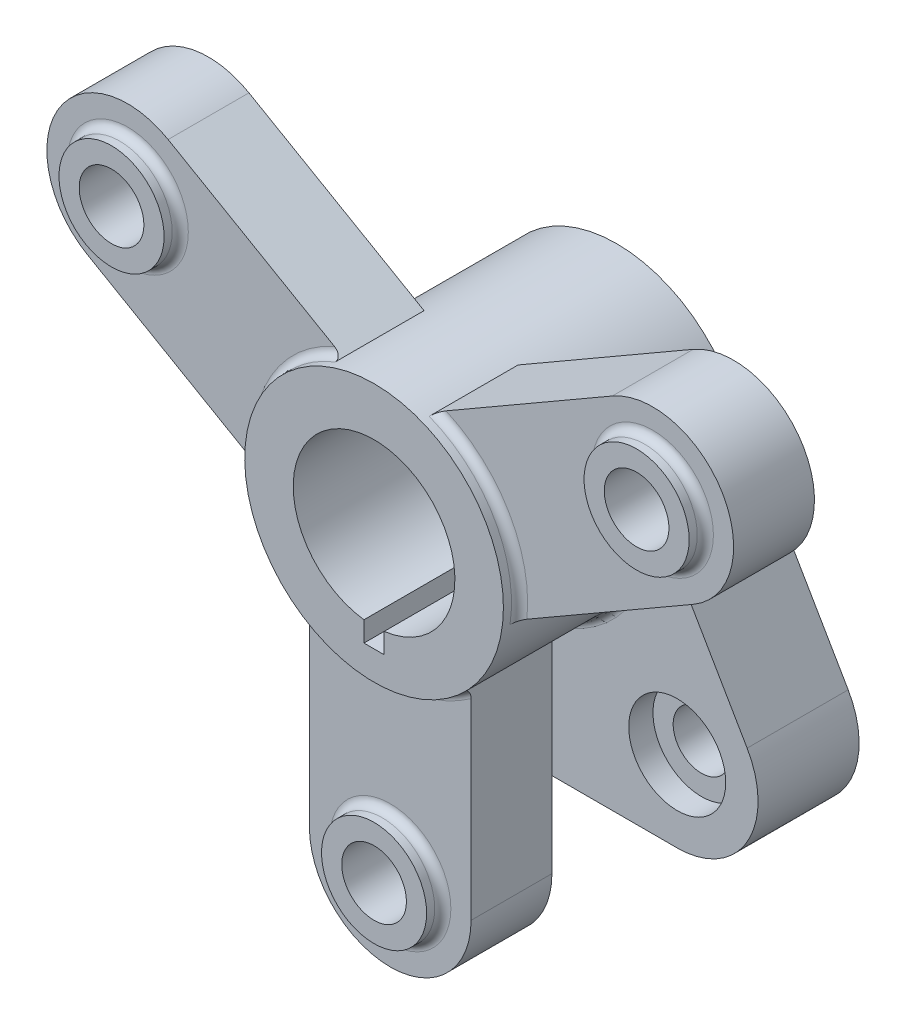
SolidWorks part; units mm, degrees
ref_plane "Front Plane" through (0, 0, 0) normal (0, 0, 1) x (1, 0, 0)
ref_plane "Top Plane" through (0, 0, 0) normal (0, 1, 0) x (1, 0, 0)
ref_plane "Right Plane" through (0, 0, 0) normal (1, 0, 0) x (0, 0, -1)
sketch "Sketch1" plane through (0, 0, 0) normal (0, 0, 1) x (1, 0, 0)
  line L0 (0, 0) -> (0, -37.1327) construction
  line L1 (-27.6745, 16.0662) -> (-57.2966, -34.9586)
  line L2 (-40, -65) -> (40, -65)
  line L3 (2.5, -19.8431) -> (2.5, -24.8431)
  line L4 (2.5, -24.8431) -> (-2.5, -24.8431)
  line L5 (-2.5, -19.8431) -> (-2.5, -24.8431)
  line L6 (57.2966, -34.9586) -> (27.6745, 16.0662)
  circle A0 centre (0, 0) radius 32
  arc A1 (2.5, -19.8431) -> (-2.5, -19.8431) centre (0, 0) ccw
  arc A2 (40, -65) -> (57.2966, -34.9586) centre (40, -45) ccw
  arc A3 (-40, -65) -> (-57.2966, -34.9586) centre (-40, -45) cw
  point P16 (-152.4426, 25.7275)
  point P17 (-154.918, 20.0151)
  dimension "D1" = 40
  dimension "D2" = 64
  dimension "D6" = 20
  dimension "D3" = 24.8431
  dimension "D4" = 5
  dimension "D5" = 5
  dimension "D7" = 80
  dimension "D8" = 45
  dimension "D9" = 40
extrude "Boss-Extrude1" add sketch "Sketch1" along normal blind 60 contours A1 L3 L4 A0 L5 region at (0, 31.0949, 0)
extrude "Boss-Extrude2" add sketch "Sketch1<3>" along normal blind 25 contours A3 L2 A2 L6 A0 L1 region at (0, -40.4686, 0)
sketch "Sketch1<3>" plane through (0, 0, 0) normal (0, 0, 1) x (1, 0, 0) same geometry as "Sketch1"
hole_wizard "CBORE for M5 Hex Head Bolt1" positions "Sketch4" profile "Sketch3" counterbore size "M5" standard "ANSI Metric" end condition through all
sketch "Sketch4" plane through (0, 0, 25) normal (0, 0, 1) x (1, 0, 0)
  point P0 (-40, -45)
  point P3 (40, -45)
sketch "Sketch3" plane through (-40, -45, 25) normal (1, 0, 0) x (0, -1, 0)
  line L0 (0, 0) -> (0, 25)
  line L1 (0, 25) -> (7, 25)
  line L3 (7, 25) -> (7, 6)
  line L4 (7, 6) -> (12, 6)
  line L5 (12, 6) -> (12, 0)
  line L7 (12, 0) -> (0, 0)
  line L11 (0, -6.35) -> (0, 107.95) construction
  dimension "Thru Hole Dia." = 14
  dimension "Thru Hole Depth" = 25
  dimension "C'Bore Dia." = 24
  dimension "C'Bore Depth" = 6
sketch "Sketch5" plane through (0, 0, 60) normal (0, 0, 1) x (1, 0, 0)
  line L0 (0, 0) -> (0, 86.5076) construction
  line L1 (0, 86.5076) -> (0, -102.1769) construction
  line L2 (0, 0) -> (64.9519, 37.5) construction
  line L3 (54.9519, 54.8205) -> (11.6333, 29.8105)
  line L4 (74.9519, 20.1795) -> (31.6333, -4.8305)
  circle A0 centre (0, 0) radius 75 construction
  circle A1 centre (64.9519, 37.5) radius 20
  circle A2 centre (64.9519, 37.5) radius 13
  circle A3 centre (64.9519, 37.5) radius 8
  circle A4 centre (0, 0) radius 32 construction
  circle M1 centre (0, 0) radius 32
  dimension "D1" = 150
  dimension "D3" = 16
  dimension "D4" = 26
  dimension "D5" = 40
  dimension "D2" = 60
extrude "Boss-Extrude3" add sketch "Sketch5" against normal blind 20 from offset 4 contours A1 L3 L4 M1 | A1 A2 region at (38.7969, 22.3994, 60) region at (74.6691, 54.3306, 60) offset against normal yes
extrude "Boss-Extrude4" add sketch "Sketch5<3>" against normal blind 24 contours A2 A3 region at (52.3196, 37.5, 60)
sketch "Sketch5<3>" plane through (0, 0, 60) normal (0, 0, 1) x (1, 0, 0) same geometry as "Sketch5"
pattern_circular "CirPattern1" count 3 over 360 about axis through (0, 0, 60) along (0, 0, -1) of "Boss-Extrude4", "Boss-Extrude3"
fillet "Fillet8" radius 2 3 edges at (77.9519, 37.5, 56) (-6.5, -86.2583, 56) (-71.4519, 48.7583, 56)
fillet "Fillet9" radius 2 3 edges at (-27.7128, 16, 56) (0, -32, 56) (27.7128, 16, 56)
fillet "Fillet10" radius 2 1 edges at (0, -32, 25)
